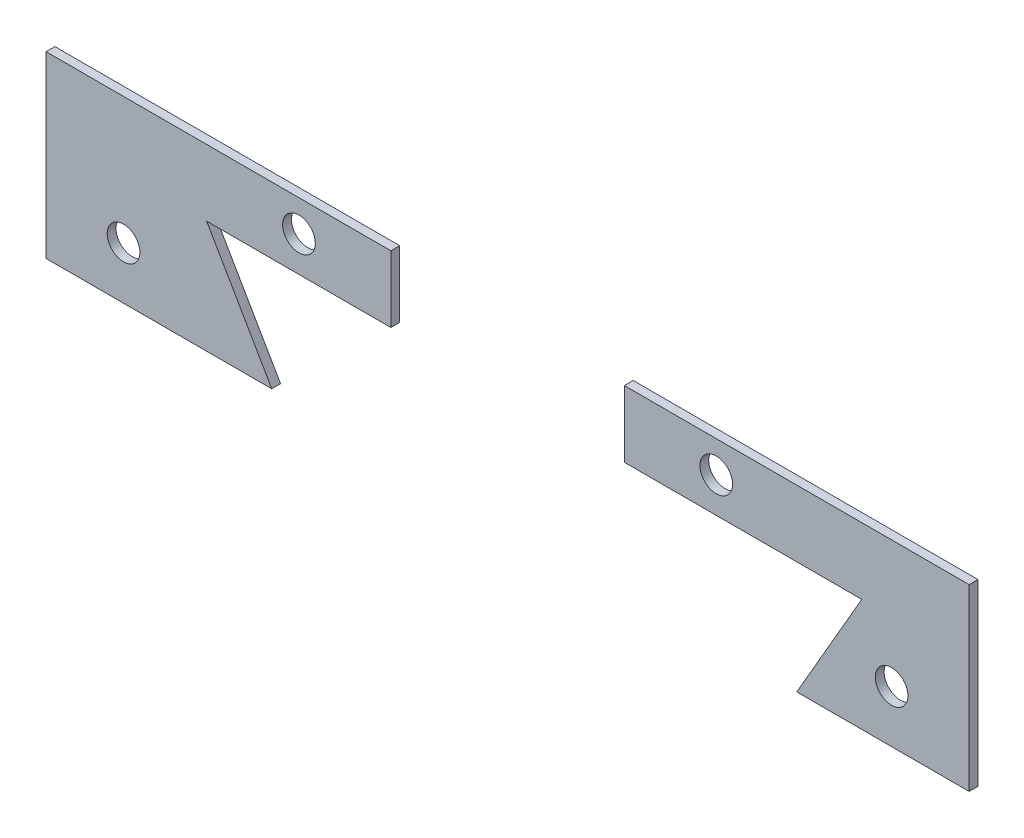
SolidWorks part; units mm, degrees
material "Plain Carbon Steel"
ref_plane "Front Plane" through (0, 0, 0) normal (0, 0, 1) x (1, 0, 0)
ref_plane "Top Plane" through (0, 0, 0) normal (0, 1, 0) x (1, 0, 0)
ref_plane "Right Plane" through (0, 0, 0) normal (1, 0, 0) x (0, 0, -1)
sketch "Sketch4" plane through (0, 0, 0) normal (0, 0, 1) x (1, 0, 0)
  point P0 (0, 0)
  line B0 (-63.5, -15.875) -> (63.5, -15.875)
  line B1 (63.5, -15.875) -> (63.5, 0)
  line B2 (63.5, 0) -> (38.4596, 0)
  line B3 (38.4596, 0) -> (47.625, 15.875)
  line B4 (47.625, 15.875) -> (16.0563, 15.875)
  line B5 (-40.2927, 15.875) -> (-31.1272, 0)
  line B6 (-31.1272, 0) -> (-63.5, 0)
  line B7 (-38.4596, 0) -> (-47.625, 15.875)
  line B8 (-16.0563, -3.175) -> (16.0563, -3.175)
  line B9 (16.0563, -3.175) -> (16.0563, 15.875)
  line B10 (-16.0563, 15.875) -> (-40.2927, 15.875)
  line B11 (-63.5, 0) -> (-63.5, 31.75)
  line B12 (-63.5, 31.75) -> (63.5, 31.75)
  line B13 (63.5, 31.75) -> (63.5, 0)
  line B14 (-16.0563, 15.875) -> (16.0563, 15.875)
  line B15 (-38.4596, 0) -> (38.4596, 0) construction
  line B16 (-28.702, 21.082) -> (28.702, 21.082) construction
  line B17 (-52.832, 7.9375) -> (52.832, 7.9375) construction
  circle B18 centre (0, 6.35) radius 18.669 construction
sketch_block_instance "dovetail pair-1"
sketch_block "dovetail pair" parameters "D8"=37.338, "D1"=60, "D2"=127, "D3"=6.35, "D4"=15.875, "D5"=31.75, "D6"=95.25, "D7"=19.05, "D9"=60, "D10"=31.75, "D11"=50.8, "D12"=23.876, "D13"=7.874, "D14"=10.668, "D15"=34.798, "D16"=21.082, "D17"=7.9375
sketch "Sketch1" plane through (0, 0, 0) normal (0, 0, 1) x (1, 0, 0)
  line L0 (-63.5, 31.75) -> (63.5, 31.75) construction
  line L1 (-63.5, 0) -> (-63.5, 31.75) construction
  line L2 (-31.1272, 0) -> (-63.5, 0) construction
  line L3 (-40.2927, 15.875) -> (-31.1272, 0) construction
  line L4 (-16.0563, 15.875) -> (-40.2927, 15.875) construction
  line L5 (-16.0563, 15.875) -> (16.0563, 15.875) construction
  line L6 (47.625, 15.875) -> (16.0563, 15.875) construction
  line L7 (38.4596, 0) -> (47.625, 15.875) construction
  line L8 (63.5, 0) -> (38.4596, 0) construction
  line L9 (63.5, 31.75) -> (63.5, 0) construction
  line L10 (-63.5, 31.75) -> (63.5, 31.75) construction
  line L11 (-63.5, 0) -> (-63.5, 31.75) construction
  line L12 (-63.5, 0.762) -> (-32.447, 0.762)
  line L13 (-32.447, 0.762) -> (-41.3925, 16.256)
  line L14 (16.0563, 15.875) -> (16.0563, 16.256) construction
  line L15 (-41.3925, 16.256) -> (-16.0563, 16.256)
  line L16 (-16.0563, 16.256) -> (-16.0563, 25.4)
  line L17 (-16.0563, 25.4) -> (-63.5, 25.4)
  line L18 (-31.1272, 0) -> (-63.5, 0) construction
  line L19 (-63.5, 25.4) -> (-63.5, 0.762)
  line L21 (-40.2927, 15.875) -> (-31.1272, 0) construction
  line L24 (-16.0563, 15.875) -> (-16.0563, 16.256) construction
  line L25 (16.0563, 16.256) -> (48.7249, 16.256)
  line L26 (48.7249, 16.256) -> (39.7794, 0.762)
  line L27 (39.7794, 0.762) -> (63.5, 0.762)
  line L28 (63.5, 0.762) -> (63.5, 25.4)
  line L30 (63.5, 25.4) -> (16.0563, 25.4)
  line L33 (-16.0563, 15.875) -> (-40.2927, 15.875) construction
  line L34 (-16.0563, 15.875) -> (16.0563, 15.875) construction
  line L35 (47.625, 15.875) -> (16.0563, 15.875) construction
  line L36 (38.4596, 0) -> (47.625, 15.875) construction
  line L37 (63.5, 0) -> (38.4596, 0) construction
  line L38 (63.5, 31.75) -> (63.5, 0) construction
  line L39 (16.0563, 25.4) -> (16.0563, 16.256)
  dimension "D1" = 25.4
  dimension "D2" = 0.762
  dimension "D3" = 0.762
  dimension "D4" = 0.762
  dimension "D5" = 0.762
extrude "Boss-Extrude1" add sketch "Sketch1" along normal blind 1.2141
hole_wizard "#8 Clearance Hole1" positions "Sketch2" profile "Sketch3" hole size "#8" standard "ANSI Inch" end condition through all
sketch "Sketch2" plane through (0, -15.875, 1.2141) normal (0, 0, 1) x (1, 0, 0)
  point P32 (-28.702, 36.957)
  point P34 (-52.832, 23.8125)
  point P36 (28.702, 36.957)
  point P38 (52.832, 23.8125)
sketch "Sketch3" plane through (-28.702, 21.082, 1.2141) normal (1, 0, 0) x (0, -1, 0)
  line L0 (0, 0) -> (0, 1.2141)
  line L1 (0, 1.2141) -> (2.2479, 1.2141)
  line L2 (2.2479, 1.2141) -> (2.2479, 0)
  line L3 (2.2479, 0) -> (0, 0)
  line L4 (0, -6.35) -> (0, 107.95) construction
  dimension "Thru Hole Dia." = 4.4958
  dimension "Thru Hole Depth" = 1.2141
equation "\"dovetail-angle\" = 60"
equation "\"dovetail-stock-width\" = 5"
equation "\"dovetail-stock-height\" = 1.25"
equation "\"dovetail-depth\" = 0.5 * \"dovetail-stock-height\""
equation "\"dovetail-throat-width\" = \"dovetail-stock-width\" - (2 * \"dovetail-depth\")"
equation "\"delta-x\" = 6"
equation "\"delta-y\" = 3"
equation "\"gib-thickness\" = 0.25"
equation "\"x-slide-length\" = \"dovetail-stock-width\" + \"delta-x\""
equation "\"y-slide-length\" = \"dovetail-stock-width\" + \"delta-y\""
equation "\"dog-point-diam\" = .149"
equation "\"dog-point-length\" = .067"
equation "\"dovetail-double-height\" = 2 * \"dovetail-depth\" + 0.5"
equation "\"acme-major-diam\" = .5"
equation "\"acme-pitch-diam\" = 0.45"
equation "\"acme-minor-diam\" = 0.4"
equation "\"acme-nut-od\" = 1.47"
equation "\"acme-nut-length\" = 1"
equation "\"acme-nut-trim-height\" = .75"
equation "\"screw-bearing-od\" = 0.5"
equation "\"screw-bearing-length\" = .375"
equation "\"screw-bearing-id\" = .375"
equation "\"end-plate-thickness\" = \"screw-bearing-length\""
equation "\"screw-add-length\" = 2 * \"end-plate-thickness\" + 1 + 0.5"
equation "\"x-screw-length\" = \"x-slide-length\" + \"screw-add-length\""
equation "\"y-screw-length\" = \"y-slide-length\" + \"screw-add-length\""
equation "\"acme-nut-mount-hole-space-horz\" = 0.95"
equation "\"acme-nut-mount-hole-space-vert\" = 0.5 * \"acme-nut-length\""
equation "\"vise-hole-center-dist\" = 6.75"
equation "\"wiper_plate_clearance\" = .03"
equation "\"D2@Sketch1\"=\"wiper_plate_clearance\""
equation "\"D3@Sketch1\"=\"wiper_plate_clearance\""
equation "\"D4@Sketch1\"=\"wiper_plate_clearance\""
equation "\"D5@Sketch1\"=\"wiper_plate_clearance\""
equation "\"D2@dovetail pair\"=\"dovetail-stock-width\""
equation "\"D1@dovetail pair\"=\"dovetail-angle\""
equation "\"D3@dovetail pair\"=\"gib-thickness\""
equation "\"D4@dovetail pair\"=\"dovetail-depth\""
equation "\"D5@dovetail pair\"=\"dovetail-stock-height\""
equation "\"D6@dovetail pair\"=\"dovetail-throat-width\""
equation "\"D10@dovetail pair\"=\"dovetail-stock-height\""
equation "\"D7@dovetail pair\"=\"acme-nut-trim-height\""
equation "\"D8@dovetail pair\"=\"acme-nut-od\""
equation "\"D9@dovetail pair\"=\"dovetail-angle\""
equation "\"D17@dovetail pair\"=\"dovetail-depth\"/2"
